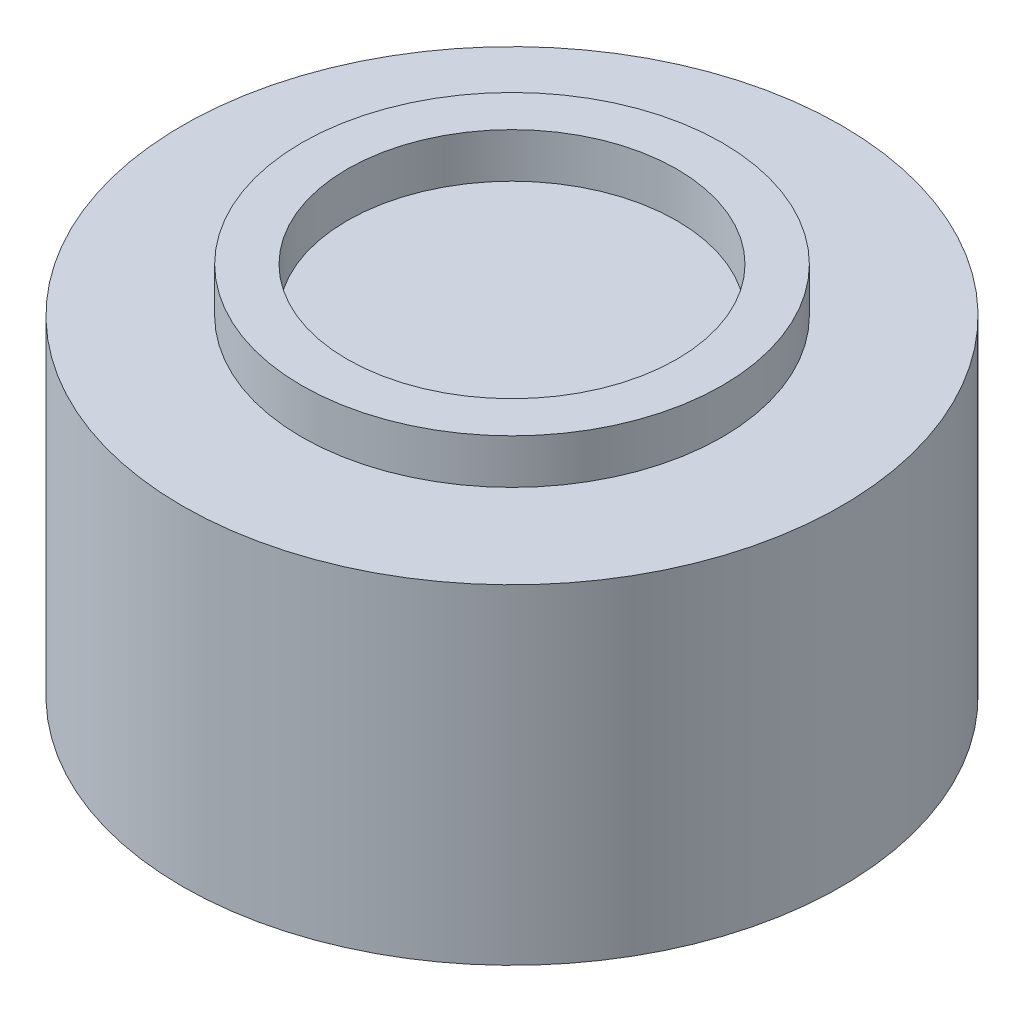
SolidWorks part; units mm, degrees
ref_plane "Front Plane" through (0, 0, 0) normal (0, 0, 1) x (1, 0, 0)
ref_plane "Top Plane" through (0, 0, 0) normal (0, 1, 0) x (1, 0, 0)
ref_plane "Right Plane" through (0, 0, 0) normal (1, 0, 0) x (0, 0, -1)
sketch "Sketch1" plane through (0, 0, 0) normal (0, 1, 0) x (1, 0, 0)
  circle A0 centre (0, 0) radius 6.35
  dimension "D1" = 12.7
extrude "Boss-Extrude1" add sketch "Sketch1" along normal blind 6.35
sketch "Sketch2" plane through (0, 0, 0) normal (1, 0, 0) x (0, 0, -1)
  line L0 (-3.175, 1.5914) -> (-4.0516, 1.5914)
  line L1 (-4.0516, 1.5914) -> (-6.2111, 0)
  line L4 (-6.35, 0) -> (-4.0516, 1.8587)
  line L5 (-4.0516, 1.8587) -> (-3.175, 1.8587)
  line L7 (-4.0516, 1.8587) -> (-4.0516, 7.2105)
  line L8 (-4.0516, 7.2105) -> (-3.175, 7.2105)
  line L9 (-3.175, 7.2105) -> (-3.175, 1.8587)
  line L11 (-6.35, 0) -> (6.35, 0) construction
  line L12 (-6.35, 0) -> (-6.2111, 0)
  line L13 (-3.175, 1.5914) -> (-3.175, 1.8587)
  line L14 (0, 0) -> (0, 4.302)
  dimension "D2" = 3.175
revolve "Revolve1" add sketch "Sketch2" angle 360 about L14 region at (0, 1.6282, 3.6133) region at (0, 4.5346, 3.6133)
